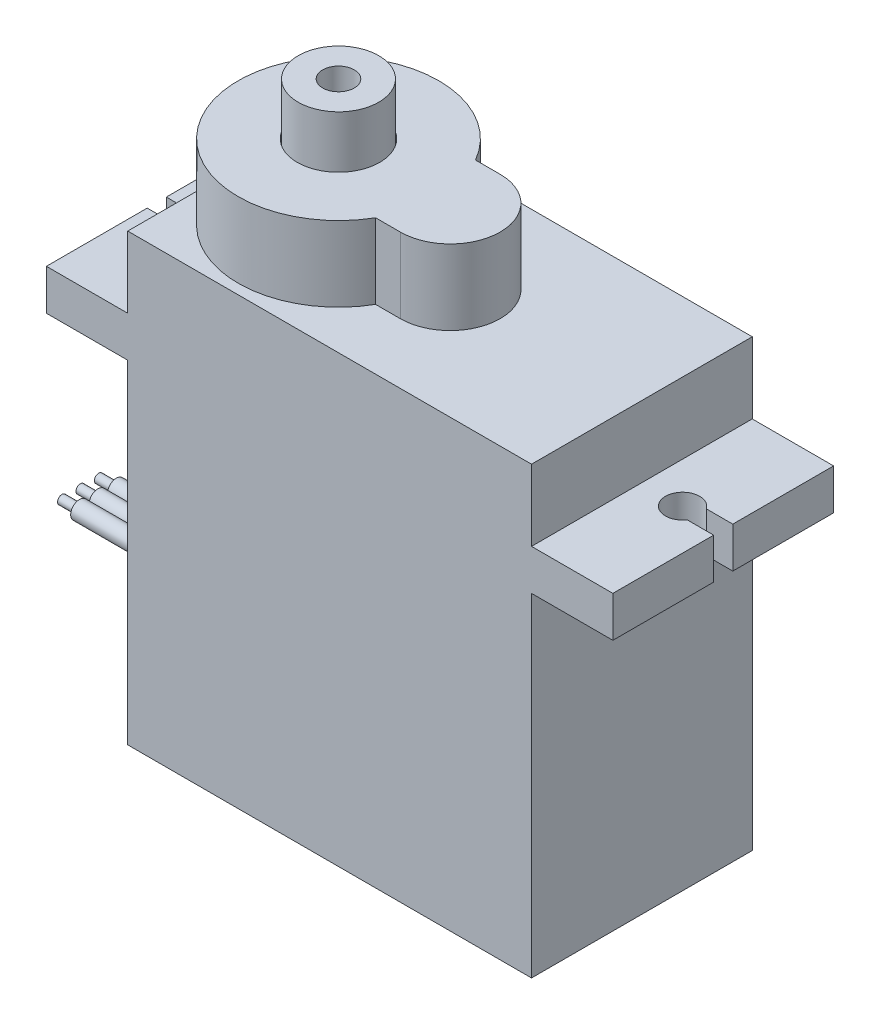
SolidWorks part; units mm, degrees
ref_plane "Front Plane" through (0, 0, 0) normal (0, 0, 1) x (1, 0, 0)
ref_plane "Top Plane" through (0, 0, 0) normal (0, 1, 0) x (1, 0, 0)
ref_plane "Right Plane" through (0, 0, 0) normal (1, 0, 0) x (0, 0, -1)
ref_axis "X-Axis" through (-88.99, 0, 0) along (1, 0, 0)
ref_axis "Y-Axis" through (0, 0, -88.99) along (0, 0, 1)
ref_axis "Z-Axis" through (0, 55, 0) along (0, -1, 0)
sketch "Sketch1" plane through (0, 0, 0) normal (0, 0, 1) x (1, 0, 0)
  line L0 (0, 0) -> (0, 10.3) construction
  line L1 (-7.13, 6.38) -> (15.9, 6.38)
  line L2 (-7.13, 6.38) -> (-7.13, 2.32)
  line L3 (-7.13, -19) -> (15.9, -19)
  line L4 (15.9, 6.38) -> (15.9, 2.32)
  line L5 (15.9, 2.32) -> (20.54, 2.32)
  line L6 (-11.77, 2.32) -> (-7.13, 2.32)
  line L7 (-11.77, 2.32) -> (-11.77, 0)
  line L8 (-11.77, 0) -> (-7.13, 0)
  line L9 (20.54, 2.32) -> (20.54, 0)
  line L10 (15.9, 0) -> (20.54, 0)
  line L11 (-7.13, 0) -> (-7.13, -19)
  line L12 (15.9, 0) -> (15.9, -19)
  line L14 (15.9, 0) -> (-7.13, 0) construction
  point P3 (4.385, 0)
  dimension "D1" = 2.32
  dimension "D2" = 32.31
  dimension "D3" = 23.03
  dimension "D4" = 4.06
  dimension "D5" = 19
  dimension "D6" = 7.13
  dimension "D7" = 15.9
  dimension "D10" = 29.3
  dimension "D11" = 4.385
extrude "Boss-Extrude1" add sketch "Sketch1" along normal mid plane 12.59
sketch "Sketch2" plane through (0, 6.38, 0) normal (0, 1, 0) x (1, 0, 0)
  line L0 (-1.405, 0) -> (4.97, 0) construction
  line L1 (3.5602, -2.85) -> (4.97, -2.85)
  line L2 (4.97, 2.85) -> (3.5602, 2.85)
  line L3 (-1.405, 0) -> (-7.13, 0) construction
  line L4 (4.97, 0) -> (7.82, 0) construction
  line L5 (-7.13, -6.295) -> (-7.13, 6.295) construction
  arc A0 (3.5602, 2.85) -> (3.5602, -2.85) centre (-1.405, 0) ccw
  arc A1 (4.97, -2.85) -> (4.97, 2.85) centre (4.97, 0) ccw
  dimension "D1" = 11.45
  dimension "D2" = 5.7
  dimension "D3" = 14.95
extrude "Boss-Extrude2" add sketch "Sketch2" along normal blind 4.28
sketch "Sketch11" plane through (-11.77, 0, 0) normal (-1, 0, 0) x (0, 0, 1)
  line L0 (-5.86, 6.38) -> (-6.295, -13.5)
  line L1 (0, 6.38) -> (-6.295, 6.38) construction
  line L2 (6.295, -19) -> (-6.295, -19) construction
  line L3 (-6.295, 0) -> (-6.295, -19) construction
  line L4 (-5.86, 6.38) -> (-6.295, 6.38)
  line L5 (-6.295, 6.38) -> (-6.295, -13.5)
  dimension "D1" = 5.86
  dimension "D2" = 5.5
extrude "Cut-Extrude4" [suppressed] cut sketch "Sketch11" against normal through all
mirror "Mirror1" [suppressed] about plane through (0, 0, 0) normal (0, 0, 1)
sketch "Sketch4" plane through (0, 0, 0) normal (0, 1, 0) x (1, 0, 0)
  line L0 (-7.13, 0) -> (-9.45, 0) construction
  line L1 (-11.77, -6.295) -> (-11.77, 6.295) construction
  line L2 (-10.2585, 0.545) -> (-11.77, 0.545)
  line L3 (-10.2585, 0.545) -> (-10.2585, -0.545)
  line L4 (-10.2585, -0.545) -> (-11.77, -0.545)
  line L5 (-11.77, 0.545) -> (-11.77, -0.545)
  line L8 (-9.45, 0) -> (-10.2585, 0) construction
  line L9 (-9.45, 0) -> (-11.77, 0) construction
  arc A0 (3.5602, 2.85) -> (3.5602, -2.85) centre (-1.405, 0) ccw construction
  circle A1 centre (-9.45, 0) radius 0.975
  dimension "D1" = 1.09
  dimension "D2" = 1.95
extrude "Cut-Extrude1" cut sketch "Sketch4" along normal through all contours A1 | L4 L5 L2 L3
sketch "Sketch14" [suppressed] plane through (0, 0.1312, 5.9967) normal (0, 0.0219, 0.9998) x (1, 0, 0)
  line L0 (4.385, -13.6345) -> (-7.13, -13.6345) construction
  line L1 (15.9, -13.6345) -> (-7.13, -13.6345) construction
ref_plane "Plane1" [suppressed] through (4.385, -13.5, 6.295) normal (-1, 0, 0) x (0, 0, 1)
mirror "Mirror2" about plane through (4.385, -13.5, 6.295) normal (-1, 0, 0) of "Cut-Extrude1"
sketch "Sketch5" plane through (0, -19, 0) normal (0, -1, 0) x (1, 0, 0)
  line L0 (15.9, 6.295) -> (-7.13, -6.295) construction
  line L17 (-5.49, 4.35) -> (14.26, 4.35) construction
  line L18 (-5.49, 4.35) -> (-5.49, -4.35) construction
  line L19 (-5.49, -4.35) -> (14.26, -4.35) construction
  line L20 (14.26, 4.35) -> (14.26, -4.35) construction
  line L21 (-5.49, 4.35) -> (14.26, -4.35) construction
  circle A0 centre (-5.49, 4.35) radius 1
  circle A1 centre (-5.49, -4.35) radius 1
  circle A2 centre (14.26, -4.35) radius 1
  circle A3 centre (14.26, 4.35) radius 1
  circle A4 centre (-5.49, 4.35) radius 0.975
  circle A5 centre (-5.49, -4.35) radius 0.975
  circle A6 centre (14.26, -4.35) radius 0.975
  circle A7 centre (14.26, 4.35) radius 0.975
  point P36 (4.385, 0)
  dimension "D1" = 0.025
  dimension "D4" = 1.95
  dimension "D5" = 19.75
  dimension "D6" = 8.7
extrude "Cut-Extrude2" cut sketch "Sketch5" against normal blind 1
sketch "Sketch6" plane through (-7.13, 0, 0) normal (-1, 0, 0) x (0, 0, 1)
  line L0 (-1.05, -14) -> (1.05, -14) construction
  line L1 (0, -14.5) -> (0, -19) construction
  line L3 (6.295, -19) -> (-6.295, -19) construction
  circle A0 centre (0, -14) radius 0.5
  circle A1 centre (1.05, -14) radius 0.5
  circle A2 centre (-1.05, -14) radius 0.5
  dimension "D3" = 1
  dimension "D1" = 4.5
  dimension "D2" = 2.1
extrude "Boss-Extrude4" add sketch "Sketch6" along normal blind 8
sketch "Sketch7" plane through (-15.13, 0, 0) normal (-1, 0, 0) x (0, 0, 1)
  circle A0 centre (0, -14) radius 0.25
  circle A1 centre (1.05, -14) radius 0.25
  circle A2 centre (-1.05, -14) radius 0.25
  dimension "D1" = 0.5
extrude "Boss-Extrude5" add sketch "Sketch7" along normal blind 1
sketch "Sketch3" plane through (0, 10.66, 0) normal (0, 1, 0) x (1, 0, 0)
  line L0 (4.7718, -0.52) -> (4.97, -0.52)
  line L1 (4.97, 0.52) -> (4.7718, 0.52)
  line L2 (5.49, 0) -> (7.82, 0) construction
  line L3 (-4.8, 0) -> (-7.13, 0) construction
  arc A0 (4.7718, 0.52) -> (4.7718, -0.52) centre (0, 0) ccw
  arc A1 (4.97, -0.52) -> (4.97, 0.52) centre (4.97, 0) ccw
  arc A2 (4.97, -2.85) -> (4.97, 2.85) centre (4.97, 0) ccw construction
  arc A3 (3.5602, 2.85) -> (3.5602, -2.85) centre (-1.405, 0) ccw construction
  dimension "D1" = 9.6
fillet "Fillet1" radius 0.3 4 edges at (14.26, -19, -5.325) (14.26, -19, 3.375) (-5.49, -19, -5.325) (-5.49, -19, 3.375)
fillet "Fillet3" [suppressed] radius 0.2
sketch "Sketch12" plane through (0, 10.66, 0) normal (0, 1, 0) x (1, 0, 0)
  circle A0 centre (-1.405, 0) radius 2.3
  circle A1 centre (-1.405, 0) radius 0.9
  dimension "D1" = 4.6
  dimension "D2" = 1.8
extrude "Boss-Extrude6" add sketch "Sketch12" along normal blind 2.95 and the other way blind 1 separate body
sketch "Sketch13" plane through (0, 13.61, 0) normal (0, 1, 0) x (1, 0, 0)
  circle A0 centre (-1.405, 0) radius 2.35
  dimension "D1" = 4.7
extrude "Cut-Extrude5" cut sketch "Sketch13" against normal blind 5
